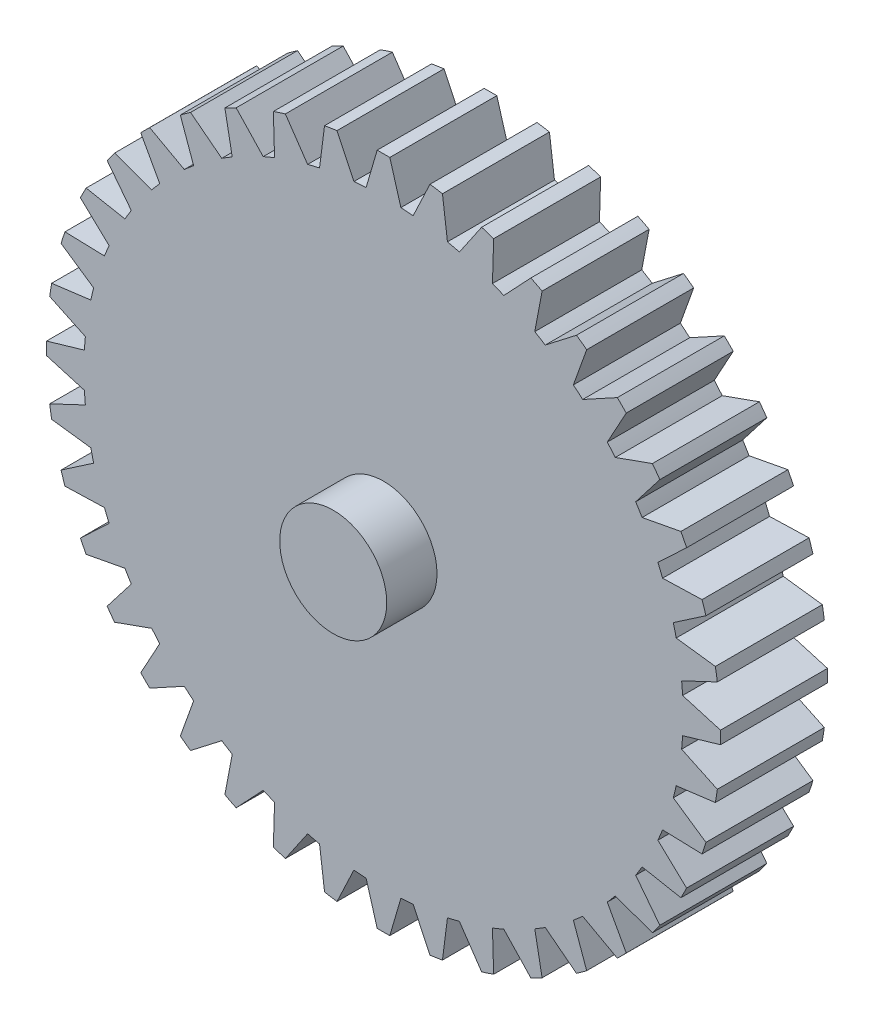
SolidWorks part; units mm, degrees
ref_plane "Front Plane" through (0, 0, 0) normal (0, 0, 1) x (1, 0, 0)
ref_plane "Top Plane" through (0, 0, 0) normal (0, 1, 0) x (1, 0, 0)
ref_plane "Right Plane" through (0, 0, 0) normal (1, 0, 0) x (0, 0, -1)
sketch "Sketch1" plane through (0, 0, 0) normal (0, 0, 1) x (1, 0, 0)
  line L0 (93.5, 343.5) -> (593.5, 343.5) construction
  line L1 (4.3441, 31.199) -> (2.7678, 27.8629)
  line L2 (5.5096, 31.0144) -> (5.9778, 27.3545)
  line L3 (9.1712, 30.1353) -> (7.0924, 27.0869)
  line L4 (10.2935, 29.7707) -> (10.1834, 26.0825)
  line L5 (13.7725, 28.3296) -> (11.2424, 25.6439)
  line L6 (-0.59, 31.4945) -> (-1.625, 27.9528)
  line L7 (0.59, 31.4945) -> (1.625, 27.9528)
  line L8 (-0.59, 31.4945) -> (0.59, 31.4945)
  line L9 (14.8239, 27.7939) -> (14.1382, 24.1684)
  line L10 (18.0347, 25.8264) -> (15.1156, 23.5694)
  line L11 (18.9893, 25.1328) -> (17.7449, 21.6591)
  line L12 (21.8528, 22.6871) -> (18.6166, 20.9147)
  line L13 (22.6871, 21.8528) -> (20.9147, 18.6166)
  line L14 (25.1328, 18.9893) -> (21.6591, 17.7449)
  line L15 (25.8264, 18.0347) -> (23.5694, 15.1156)
  line L16 (27.7939, 14.8239) -> (24.1684, 14.1382)
  line L17 (28.3296, 13.7725) -> (25.6439, 11.2424)
  line L18 (29.7707, 10.2935) -> (26.0825, 10.1834)
  line L19 (30.1353, 9.1712) -> (27.0869, 7.0924)
  line L20 (31.0144, 5.5096) -> (27.3545, 5.9778)
  line L21 (31.199, 4.3441) -> (27.8629, 2.7678)
  line L22 (31.4945, 0.59) -> (27.9528, 1.625)
  line L23 (31.4945, -0.59) -> (27.9528, -1.625)
  line L24 (31.199, -4.3441) -> (27.8629, -2.7678)
  line L25 (31.0144, -5.5096) -> (27.3545, -5.9778)
  line L26 (30.1353, -9.1712) -> (27.0869, -7.0924)
  line L27 (29.7707, -10.2935) -> (26.0825, -10.1834)
  line L28 (28.3296, -13.7725) -> (25.6439, -11.2424)
  line L29 (27.7939, -14.8239) -> (24.1684, -14.1382)
  line L30 (25.8264, -18.0347) -> (23.5694, -15.1156)
  line L31 (25.1328, -18.9893) -> (21.6591, -17.7449)
  line L32 (22.6871, -21.8528) -> (20.9147, -18.6166)
  line L33 (21.8528, -22.6871) -> (18.6166, -20.9147)
  line L34 (18.9893, -25.1328) -> (17.7449, -21.6591)
  line L35 (18.0347, -25.8264) -> (15.1156, -23.5694)
  line L36 (14.8239, -27.7939) -> (14.1382, -24.1684)
  line L37 (13.7725, -28.3296) -> (11.2424, -25.6439)
  line L38 (10.2935, -29.7707) -> (10.1834, -26.0825)
  line L39 (9.1712, -30.1353) -> (7.0924, -27.0869)
  line L40 (5.5096, -31.0144) -> (5.9778, -27.3545)
  line L41 (4.3441, -31.199) -> (2.7678, -27.8629)
  line L42 (0.59, -31.4945) -> (1.625, -27.9528)
  line L43 (-0.59, -31.4945) -> (-1.625, -27.9528)
  line L44 (-4.3441, -31.199) -> (-2.7678, -27.8629)
  line L45 (-5.5096, -31.0144) -> (-5.9778, -27.3545)
  line L46 (-9.1712, -30.1353) -> (-7.0924, -27.0869)
  line L47 (-10.2935, -29.7707) -> (-10.1834, -26.0825)
  line L48 (-13.7725, -28.3296) -> (-11.2424, -25.6439)
  line L49 (-14.8239, -27.7939) -> (-14.1382, -24.1684)
  line L50 (-18.0347, -25.8264) -> (-15.1156, -23.5694)
  line L51 (-18.9893, -25.1328) -> (-17.7449, -21.6591)
  line L52 (-21.8528, -22.6871) -> (-18.6166, -20.9147)
  line L53 (-22.6871, -21.8528) -> (-20.9147, -18.6166)
  line L54 (-25.1328, -18.9893) -> (-21.6591, -17.7449)
  line L55 (-25.8264, -18.0347) -> (-23.5694, -15.1156)
  line L56 (-27.7939, -14.8239) -> (-24.1684, -14.1382)
  line L57 (-28.3296, -13.7725) -> (-25.6439, -11.2424)
  line L58 (-29.7707, -10.2935) -> (-26.0825, -10.1834)
  line L59 (-30.1353, -9.1712) -> (-27.0869, -7.0924)
  line L60 (-31.0144, -5.5096) -> (-27.3545, -5.9778)
  line L61 (-31.199, -4.3441) -> (-27.8629, -2.7678)
  line L62 (-31.4945, -0.59) -> (-27.9528, -1.625)
  line L63 (-31.4945, 0.59) -> (-27.9528, 1.625)
  line L64 (-31.199, 4.3441) -> (-27.8629, 2.7678)
  line L65 (-31.0144, 5.5096) -> (-27.3545, 5.9778)
  line L66 (-30.1353, 9.1712) -> (-27.0869, 7.0924)
  line L67 (-29.7707, 10.2935) -> (-26.0825, 10.1834)
  line L68 (-28.3296, 13.7725) -> (-25.6439, 11.2424)
  line L69 (-27.7939, 14.8239) -> (-24.1684, 14.1382)
  line L70 (-25.8264, 18.0347) -> (-23.5694, 15.1156)
  line L71 (-25.1328, 18.9893) -> (-21.6591, 17.7449)
  line L72 (-22.6871, 21.8528) -> (-20.9147, 18.6166)
  line L73 (-21.8528, 22.6871) -> (-18.6166, 20.9147)
  line L74 (-18.9893, 25.1328) -> (-17.7449, 21.6591)
  line L75 (-18.0347, 25.8264) -> (-15.1156, 23.5694)
  line L76 (-14.8239, 27.7939) -> (-14.1382, 24.1684)
  line L77 (-13.7725, 28.3296) -> (-11.2424, 25.6439)
  line L78 (-10.2935, 29.7707) -> (-10.1834, 26.0825)
  line L79 (-9.1712, 30.1353) -> (-7.0924, 27.0869)
  line L80 (-5.5096, 31.0144) -> (-5.9778, 27.3545)
  line L81 (-4.3441, 31.199) -> (-2.7678, 27.8629)
  line L83 (16.5, -3.65) -> (-16.5, -3.65)
  line L84 (16.5, -3.65) -> (16.5, 3.65)
  line L85 (16.5, 3.65) -> (-16.5, 3.65)
  line L86 (-16.5, -3.65) -> (-16.5, 3.65)
  line L87 (16.5, -3.65) -> (-16.5, 3.65) construction
  line L88 (16.5, 3.65) -> (-16.5, -3.65) construction
  arc A2 (0.59, 31.4945) -> (-0.59, 31.4945) centre (0, 0) ccw
  arc A3 (7.0924, 27.0869) -> (5.9778, 27.3545) centre (0, 0) ccw
  arc A4 (5.5096, 31.0144) -> (4.3441, 31.199) centre (0, 0) ccw
  arc A5 (10.2935, 29.7707) -> (9.1712, 30.1353) centre (0, 0) ccw
  arc A6 (2.7678, 27.8629) -> (1.625, 27.9528) centre (0, 0) ccw
  arc A7 (-1.625, 27.9528) -> (-2.7678, 27.8629) centre (0, 0) ccw
  arc A8 (14.8239, 27.7939) -> (13.7725, 28.3296) centre (0, 0) ccw
  arc A9 (11.2424, 25.6439) -> (10.1834, 26.0825) centre (0, 0) ccw
  arc A10 (18.9893, 25.1328) -> (18.0347, 25.8264) centre (0, 0) ccw
  arc A11 (22.6871, 21.8528) -> (21.8528, 22.6871) centre (0, 0) ccw
  arc A12 (25.8264, 18.0347) -> (25.1328, 18.9893) centre (0, 0) ccw
  arc A13 (28.3296, 13.7725) -> (27.7939, 14.8239) centre (0, 0) ccw
  arc A14 (30.1353, 9.1712) -> (29.7707, 10.2935) centre (0, 0) ccw
  arc A15 (31.199, 4.3441) -> (31.0144, 5.5096) centre (0, 0) ccw
  arc A16 (31.4945, -0.59) -> (31.4945, 0.59) centre (0, 0) ccw
  arc A17 (31.0144, -5.5096) -> (31.199, -4.3441) centre (0, 0) ccw
  arc A18 (29.7707, -10.2935) -> (30.1353, -9.1712) centre (0, 0) ccw
  arc A19 (27.7939, -14.8239) -> (28.3296, -13.7725) centre (0, 0) ccw
  arc A20 (25.1328, -18.9893) -> (25.8264, -18.0347) centre (0, 0) ccw
  arc A21 (21.8528, -22.6871) -> (22.6871, -21.8528) centre (0, 0) ccw
  arc A22 (18.0347, -25.8264) -> (18.9893, -25.1328) centre (0, 0) ccw
  arc A23 (13.7725, -28.3296) -> (14.8239, -27.7939) centre (0, 0) ccw
  arc A24 (9.1712, -30.1353) -> (10.2935, -29.7707) centre (0, 0) ccw
  arc A25 (4.3441, -31.199) -> (5.5096, -31.0144) centre (0, 0) ccw
  arc A26 (-0.59, -31.4945) -> (0.59, -31.4945) centre (0, 0) ccw
  arc A27 (-5.5096, -31.0144) -> (-4.3441, -31.199) centre (0, 0) ccw
  arc A28 (-10.2935, -29.7707) -> (-9.1712, -30.1353) centre (0, 0) ccw
  arc A29 (-14.8239, -27.7939) -> (-13.7725, -28.3296) centre (0, 0) ccw
  arc A30 (-18.9893, -25.1328) -> (-18.0347, -25.8264) centre (0, 0) ccw
  arc A31 (-22.6871, -21.8528) -> (-21.8528, -22.6871) centre (0, 0) ccw
  arc A32 (-25.8264, -18.0347) -> (-25.1328, -18.9893) centre (0, 0) ccw
  arc A33 (-28.3296, -13.7725) -> (-27.7939, -14.8239) centre (0, 0) ccw
  arc A34 (-30.1353, -9.1712) -> (-29.7707, -10.2935) centre (0, 0) ccw
  arc A35 (-31.199, -4.3441) -> (-31.0144, -5.5096) centre (0, 0) ccw
  arc A36 (-31.4945, 0.59) -> (-31.4945, -0.59) centre (0, 0) ccw
  arc A37 (-31.0144, 5.5096) -> (-31.199, 4.3441) centre (0, 0) ccw
  arc A38 (-29.7707, 10.2935) -> (-30.1353, 9.1712) centre (0, 0) ccw
  arc A39 (-27.7939, 14.8239) -> (-28.3296, 13.7725) centre (0, 0) ccw
  arc A40 (-25.1328, 18.9893) -> (-25.8264, 18.0347) centre (0, 0) ccw
  arc A41 (-21.8528, 22.6871) -> (-22.6871, 21.8528) centre (0, 0) ccw
  arc A42 (-13.7725, 28.3296) -> (-14.8239, 27.7939) centre (0, 0) ccw
  arc A43 (-18.0347, 25.8264) -> (-18.9893, 25.1328) centre (0, 0) ccw
  arc A44 (-9.1712, 30.1353) -> (-10.2935, 29.7707) centre (0, 0) ccw
  arc A45 (-4.3441, 31.199) -> (-5.5096, 31.0144) centre (0, 0) ccw
  arc A46 (15.1156, 23.5694) -> (14.1382, 24.1684) centre (0, 0) ccw
  arc A47 (18.6166, 20.9147) -> (17.7449, 21.6591) centre (0, 0) ccw
  arc A48 (24.1684, 14.1382) -> (23.5694, 15.1156) centre (0, 0) ccw
  arc A49 (21.6591, 17.7449) -> (20.9147, 18.6166) centre (0, 0) ccw
  arc A50 (26.0825, 10.1834) -> (25.6439, 11.2424) centre (0, 0) ccw
  arc A51 (27.3545, 5.9778) -> (27.0869, 7.0924) centre (0, 0) ccw
  arc A52 (27.9528, 1.625) -> (27.8629, 2.7678) centre (0, 0) ccw
  arc A53 (27.8629, -2.7678) -> (27.9528, -1.625) centre (0, 0) ccw
  arc A54 (27.0869, -7.0924) -> (27.3545, -5.9778) centre (0, 0) ccw
  arc A55 (25.6439, -11.2424) -> (26.0825, -10.1834) centre (0, 0) ccw
  arc A56 (23.5694, -15.1156) -> (24.1684, -14.1382) centre (0, 0) ccw
  arc A57 (20.9147, -18.6166) -> (21.6591, -17.7449) centre (0, 0) ccw
  arc A58 (17.7449, -21.6591) -> (18.6166, -20.9147) centre (0, 0) ccw
  arc A59 (14.1382, -24.1684) -> (15.1156, -23.5694) centre (0, 0) ccw
  arc A60 (10.1834, -26.0825) -> (11.2424, -25.6439) centre (0, 0) ccw
  arc A61 (5.9778, -27.3545) -> (7.0924, -27.0869) centre (0, 0) ccw
  arc A62 (1.625, -27.9528) -> (2.7678, -27.8629) centre (0, 0) ccw
  arc A63 (-2.7678, -27.8629) -> (-1.625, -27.9528) centre (0, 0) ccw
  arc A64 (-7.0924, -27.0869) -> (-5.9778, -27.3545) centre (0, 0) ccw
  arc A65 (-11.2424, -25.6439) -> (-10.1834, -26.0825) centre (0, 0) ccw
  arc A66 (-15.1156, -23.5694) -> (-14.1382, -24.1684) centre (0, 0) ccw
  arc A67 (-18.6166, -20.9147) -> (-17.7449, -21.6591) centre (0, 0) ccw
  arc A68 (-21.6591, -17.7449) -> (-20.9147, -18.6166) centre (0, 0) ccw
  arc A69 (-24.1684, -14.1382) -> (-23.5694, -15.1156) centre (0, 0) ccw
  arc A70 (-26.0825, -10.1834) -> (-25.6439, -11.2424) centre (0, 0) ccw
  arc A71 (-27.3545, -5.9778) -> (-27.0869, -7.0924) centre (0, 0) ccw
  arc A72 (-27.9528, -1.625) -> (-27.8629, -2.7678) centre (0, 0) ccw
  arc A73 (-27.8629, 2.7678) -> (-27.9528, 1.625) centre (0, 0) ccw
  arc A74 (-27.0869, 7.0924) -> (-27.3545, 5.9778) centre (0, 0) ccw
  arc A75 (-25.6439, 11.2424) -> (-26.0825, 10.1834) centre (0, 0) ccw
  arc A76 (-23.5694, 15.1156) -> (-24.1684, 14.1382) centre (0, 0) ccw
  arc A77 (-20.9147, 18.6166) -> (-21.6591, 17.7449) centre (0, 0) ccw
  arc A78 (-17.7449, 21.6591) -> (-18.6166, 20.9147) centre (0, 0) ccw
  arc A79 (-14.1382, 24.1684) -> (-15.1156, 23.5694) centre (0, 0) ccw
  arc A80 (-10.1834, 26.0825) -> (-11.2424, 25.6439) centre (0, 0) ccw
  arc A81 (-5.9778, 27.3545) -> (-7.0924, 27.0869) centre (0, 0) ccw
  circle A82 centre (0, 0) radius 5
  point P18 (0, 31.4945)
  point P169 (0, 0)
  dimension "D1" = 63
  dimension "D2" = 3.5
  dimension "D6" = 10
  dimension "D3" = 3.25
  dimension "D4" = 1.18
  dimension "D7" = 33
  dimension "D8" = 7.3
  dimension "D5" = 40
extrude "Boss-Extrude2" add sketch "Sketch1" along normal mid plane 10 contours L80 A81 L79 A44 L78 A80 L77 A42 L76 A79 L75 A43 L74 A78 L73 A41 L72 A77 L71 A40 L70 A76 L69 A39 L68 A75 L67 A38 L66 A74 L65 A37 L64 A73 L63 A36 L62 A72 L61 A35 L60 A71 L59 A34 L58 A70 L57 A33 L56 A69 L55 | A82 L85 L86 L83 | A82 L83 L84 L85 | L85 A82 L83 | L85 A82 | L83 A82 region at (4.7883, 30.2322, 0) region at (10.4968, 0, 0) region at (0, -4.1968, 0) region at (0, 0, 0) region at (-10.4968, 0, 0) region at (0, 4.1968, 0)
extrude "Boss-Extrude3" add sketch "Sketch1<6>" along normal blind 4.7 from surface contours L85 A82 L83 | L85 A82 | L83 A82 region at (0, -4.1968, 0) region at (0, 0, 0) region at (0, 4.1968, 0) starting at face at (0, 0, 5)
sketch "Sketch1<6>" plane through (0, 0, 0) normal (0, 0, 1) x (1, 0, 0) same geometry as "Sketch1"
extrude "Cut-Extrude3" cut sketch "Sketch1<8>" along normal blind 3 from surface contours A82 L83 L84 L85 | A82 L85 L86 L83 | L85 A82 L83 region at (10.4968, 0, 0) region at (0, 0, 0) region at (-10.4968, 0, 0) starting at face at (0, 0, -5)
sketch "Sketch1<8>" plane through (0, 0, 0) normal (0, 0, 1) x (1, 0, 0) same geometry as "Sketch1"
